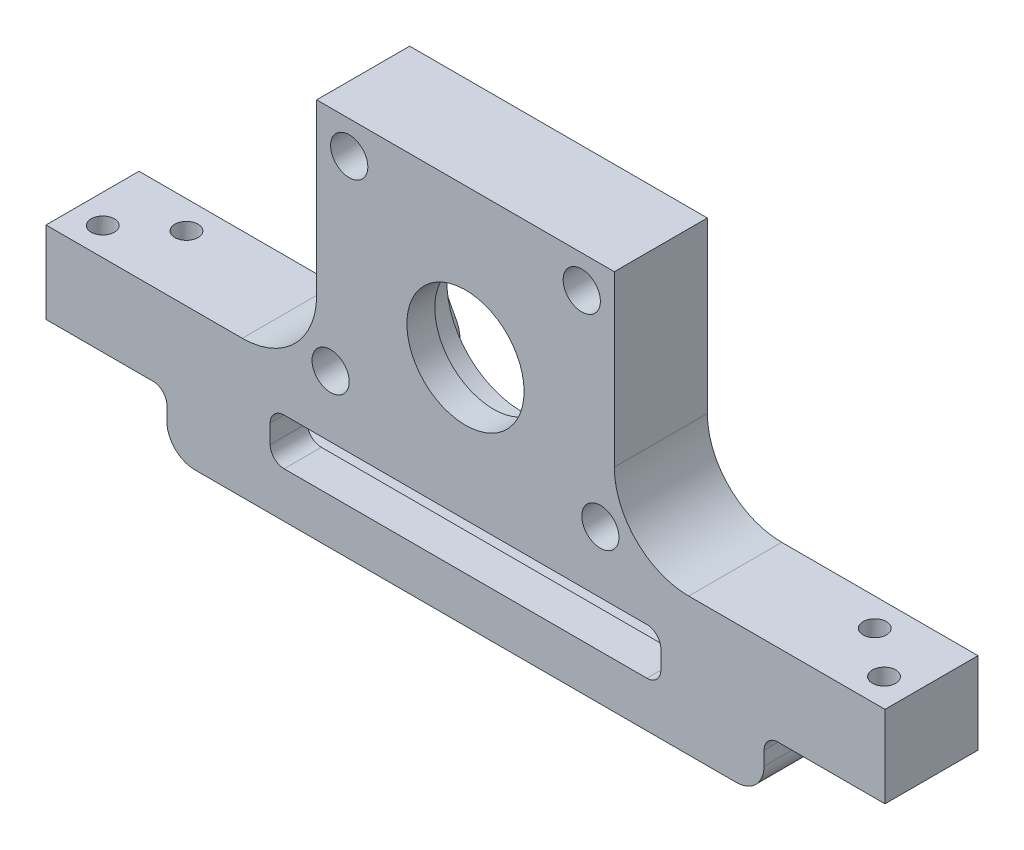
SolidWorks part; units mm, degrees
ref_plane "Front Plane" through (0, 0, 0) normal (0, 0, 1) x (1, 0, 0)
ref_plane "Top Plane" through (0, 0, 0) normal (0, 1, 0) x (1, 0, 0)
ref_plane "Right Plane" through (0, 0, 0) normal (1, 0, 0) x (0, 0, -1)
sketch "Sketch1" plane through (0, 0, 0) normal (0, 0, 1) x (1, 0, 0)
  line L0 (-16, 38) -> (16, 38)
  line L1 (-20.1, 6.5) -> (20.1, 6.5) construction
  line L2 (-20.1, 6.5) -> (-20.1, 2.3) construction
  line L3 (-20.1, 2.3) -> (20.1, 2.3) construction
  line L4 (20.1, 6.5) -> (20.1, 2.3) construction
  line L5 (-20.1, 6.5) -> (20.1, 2.3) construction
  line L6 (-20.1, 2.3) -> (20.1, 6.5) construction
  line L7 (-26.1, 7) -> (26.1, 7) construction
  line L8 (-26.1, 7) -> (-26.1, 1.8) construction
  line L9 (-26.1, 1.8) -> (26.1, 1.8) construction
  line L10 (26.1, 7) -> (26.1, 1.8) construction
  line L11 (-26.1, 7) -> (26.1, 1.8) construction
  line L12 (-26.1, 1.8) -> (26.1, 7) construction
  line L13 (29.1, 9.8) -> (-29.1, 9.8) construction
  line L14 (29.1, 9.8) -> (29.1, -1) construction
  line L15 (29.1, -1) -> (-29.1, -1) construction
  line L16 (-29.1, 9.8) -> (-29.1, -1) construction
  line L17 (29.1, 9.8) -> (-29.1, -1) construction
  line L18 (29.1, -1) -> (-29.1, 9.8) construction
  line L19 (32.1, 11.8) -> (-32.1, 11.8) construction
  line L20 (32.1, 11.8) -> (32.1, -3) construction
  line L21 (32.1, -3) -> (-32.1, -3) construction
  line L22 (-32.1, 11.8) -> (-32.1, -3) construction
  line L23 (32.1, 11.8) -> (-32.1, -3) construction
  line L24 (32.1, -3) -> (-32.1, 11.8) construction
  line L25 (16, 38) -> (16, 11.8)
  line L26 (-16, 38) -> (-16, 11.8)
  line L27 (-16, 11.8) -> (-45.1, 11.8)
  line L28 (-45.1, 11.8) -> (-45.1, 3)
  line L29 (-45.1, 3) -> (-32.1, 3)
  line L30 (-32.1, 3) -> (-32.1, -3)
  line L31 (-32.1, -3) -> (32.1, -3)
  line L32 (32.1, -3) -> (32.1, 3)
  line L33 (32.1, 3) -> (45.1, 3)
  line L34 (45.1, 3) -> (45.1, 11.8)
  line L35 (45.1, 11.8) -> (16, 11.8)
  line L37 (-21, 6.9) -> (21, 6.9)
  line L38 (-21, 6.9) -> (-21, 1.9)
  line L39 (-21, 1.9) -> (21, 1.9)
  line L40 (21, 6.9) -> (21, 1.9)
  line L41 (-21, 6.9) -> (21, 1.9) construction
  line L42 (-21, 1.9) -> (21, 6.9) construction
  circle A0 centre (0, 22) radius 6.3
  circle A1 centre (0, 22) radius 13 construction
  point P2 (0, 4.4)
  point P5 (0, 4.4)
  point P13 (0, 4.4)
  point P18 (0, 4.4)
  point P34 (0, 4.4)
  dimension "D1" = 12.6
  dimension "D11" = 26
  dimension "D2" = 40.2
  dimension "D3" = 4.2
  dimension "D4" = 6
  dimension "D5" = 0.5
  dimension "D6" = 3
  dimension "D7" = 2.8
  dimension "D8" = 3
  dimension "D9" = 2
  dimension "D10" = 3
  dimension "D12" = 22
  dimension "D13" = 16
  dimension "D14" = 32
  dimension "D15" = 16
  dimension "D16" = 13
  dimension "D17" = 42
  dimension "D18" = 5
  dimension "D19" = 6
extrude "Boss-Extrude1" add sketch "Sketch1" along normal blind 10
fillet "Fillet1" radius 1.5 4 edges at (-21, 1.9, 5) (21, 1.9, 5) (21, 6.9, 5) (-21, 6.9, 5)
sketch "Sketch8" plane through (0, 0, 0) normal (0, 0, -1) x (-1, 0, 0)
  circle A0 centre (0, 22) radius 8
  dimension "D1" = 16
extrude "Cut-Extrude9" cut sketch "Sketch8" against normal offset from surface (7 mm away) 3 up to face at (6.3, 22, 10)
sketch "Sketch2" plane through (0, 0, 0) normal (0, 0, 1) x (1, 0, 0)
  circle A0 centre (0, 22) radius 13
  dimension "D1" = 26
extrude "Cut-Extrude1" cut sketch "Sketch2" along normal offset from surface (4 mm away) 6 up to face at (6.3, 22, 10)
sketch "Sketch3" plane through (0, 0, 0) normal (0, 0, 1) x (1, 0, 0)
  line L1 (-29.1, 9.9) -> (29.1, 9.9)
  line L2 (-29.1, 9.9) -> (-29.1, -1.1)
  line L3 (-29.1, -1.1) -> (29.1, -1.1)
  line L4 (29.1, 9.9) -> (29.1, -1.1)
  line L5 (-29.1, 9.9) -> (29.1, -1.1) construction
  line L6 (-29.1, -1.1) -> (29.1, 9.9) construction
  line L7 (0, 6.9) -> (0, 1.9) construction
  line L8 (19.5, 6.9) -> (-19.5, 6.9) construction
  line L9 (-19.5, 1.9) -> (19.5, 1.9) construction
  line L10 (-21, 4.4) -> (21, 4.4) construction
  line L11 (-21, 5.4) -> (-21, 3.4) construction
  line L12 (21, 3.4) -> (21, 5.4) construction
  line L14 (-20.1, 6.5) -> (20.1, 6.5) construction
  line L15 (-20.1, 6.5) -> (-20.1, 2.3) construction
  line L16 (-20.1, 2.3) -> (20.1, 2.3) construction
  line L17 (20.1, 6.5) -> (20.1, 2.3) construction
  line L18 (-20.1, 6.5) -> (20.1, 2.3) construction
  line L19 (-20.1, 2.3) -> (20.1, 6.5) construction
  point P0 (0, 4.4)
  point P17 (0, 4.4)
  dimension "D1" = 4.2
  dimension "D2" = 40.2
  dimension "D3" = 9
  dimension "D4" = 3.4
extrude "Cut-Extrude3" cut sketch "Sketch3" along normal offset from surface (6 mm away) 4 up to face at (6.3, 22, 10)
fillet "Fillet5" radius 8 2 edges at (-16, 11.8, 5) (16, 11.8, 5)
sketch "Sketch5" plane through (0, 0, 0) normal (0, 0, -1) x (-1, 0, 0)
  line L0 (-16, 38) -> (16, 38) construction
  line L1 (-16, 19.8) -> (-16, 38) construction
  line L2 (16, 38) -> (16, 19.8) construction
  circle A0 centre (-12.5, 34.5) radius 2
  circle A1 centre (12.5, 34.5) radius 2
  circle A2 centre (-14.5, 13.5) radius 2
  circle A3 centre (14.5, 13.5) radius 2
  circle A4 centre (-14.5, 13.5) radius 3.5 construction
  circle A5 centre (14.5, 13.5) radius 3.5 construction
  dimension "D1" = 4
  dimension "D5" = 24.5
  dimension "D8" = 7
  dimension "D2" = 3.5
  dimension "D3" = 3.5
  dimension "D4" = 3.5
  dimension "D6" = 1.5
  dimension "D7" = 1.5
extrude "Cut-Extrude7" cut sketch "Sketch5" against normal up to next
fillet "Fillet4" radius 1.5 2 edges at (-32.1, 3, 5) (32.1, 3, 5)
hole_wizard "Tap Drill for M3 Tap1" positions "Sketch11" profile "Sketch10" hole size "M3" standard "ISO"
sketch "Sketch11" plane through (0, 3, 0) normal (0, -1, 0) x (-1, 0, 0)
  line L1 (45.1, -10) -> (33.6, -10) construction
  line L2 (45.1, 0) -> (33.6, 0) construction
  point P0 (42, -7)
  point P2 (37, -3)
  point P4 (-37, -3)
  point P6 (-42, -7)
  dimension "D1" = 37
  dimension "D2" = 5
  dimension "D3" = 3
  dimension "D4" = 3
  dimension "D5" = 5
  dimension "D6" = 37
sketch "Sketch10" plane through (-42, 3, 7) normal (1, 0, 0) x (0, 0, -1)
  line L0 (0, 0) -> (0, 13.7511)
  line L1 (0, 13.7511) -> (1.25, 13)
  line L2 (1.25, 13) -> (1.25, 0)
  line L5 (1.25, 0) -> (0, 0)
  line L10 (0, 13.7511) -> (-1.25, 13) construction
  line L11 (0, -6.35) -> (0, 107.95) construction
  dimension "Hole Dia." = 2.5
  dimension "Hole Depth" = 13
  dimension "Drill Angle" = 118
fillet "Fillet7" radius 3.5 2 edges at (-4.7529, 9.9, 2) (4.7529, 9.9, 2)
fillet "Fillet8" radius 1.5 4 edges at (29.1, -1.1, 3) (-29.1, -1.1, 3) (-29.1, 9.9, 3) (29.1, 9.9, 3)
fillet "Fillet9" radius 3 2 edges at (-32.1, -3, 5) (32.1, -3, 5)
